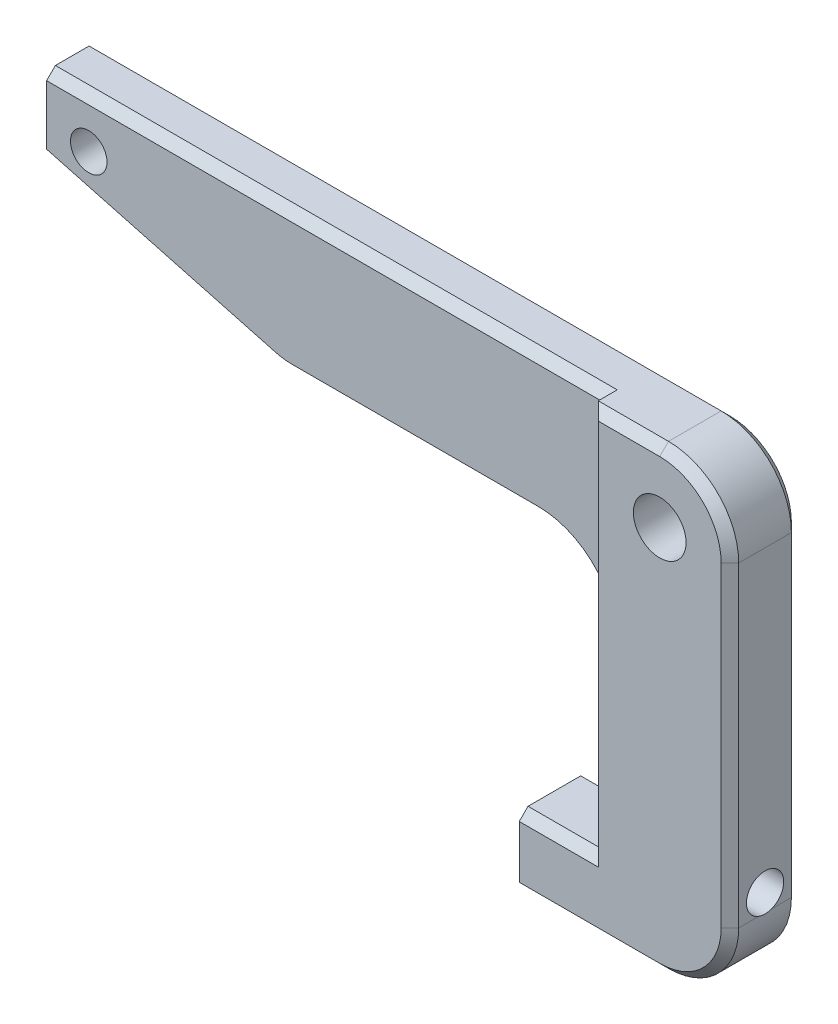
SolidWorks part; units mm, degrees
ref_plane "Plane1" through (0, 0, 0) normal (0, 0, 1) x (1, 0, 0)
ref_plane "Plane2" through (0, 0, 0) normal (0, 1, 0) x (1, 0, 0)
ref_plane "Plane3" through (0, 0, 0) normal (1, 0, 0) x (0, 0, -1)
other "Configuration Table"
sketch "Sketch1" plane through (0, 0, 0) normal (0, 0, 1) x (1, 0, 0)
  line L0 (-114.3, 12.7) -> (-114.3, -12.7)
  line L1 (-114.3, -12.7) -> (-12.7, -12.7)
  line L2 (12.7, 12.7) -> (-114.3, 12.7)
  line L3 (12.7, 12.7) -> (12.7, -69.85)
  line L4 (-12.7, -12.7) -> (-12.7, -57.15)
  line L5 (12.7, -69.85) -> (-25.4, -69.85)
  line L6 (-25.4, -69.85) -> (-25.4, -57.15)
  line L7 (-25.4, -57.15) -> (-12.7, -57.15)
  dimension "D1" = 82.55
  dimension "D2" = 127
  dimension "D3" = 44.45
  dimension "D4" = 25.4
  dimension "D5" = 12.7
  dimension "D6" = 12.7
  dimension "D7" = 25.4
  dimension "D8" = 38.1
extrude "Base-Extrude" add sketch "Sketch1" along normal blind 12.7
sketch "Sketch2" plane through (0, 0, 12.7) normal (0, 0, 1) x (1, 0, 0)
  circle A0 centre (0, 0) radius 4.7625
  dimension "D1" = 9.525
extrude "Cut-Extrude1" cut sketch "Sketch2" against normal through all
sketch "Sketch3" plane through (-40.8261, 4.3037, 12.7) normal (0, 0, 1) x (1, 0, 0)
  line L0 (-73.4739, 8.3963) -> (-73.4739, -17.0037) construction
  line L1 (53.5261, 8.3963) -> (-73.4739, 8.3963) construction
  circle A0 centre (-65.8539, -0.4937) radius 3.302
  dimension "D1" = 6.604
  dimension "D2" = 7.62
  dimension "D3" = 8.89
extrude "Cut-Extrude2" cut sketch "Sketch3" against normal through all
chamfer "Chamfer1" distance 11.43 angle 75 1 edges at (-114.3, -12.7, 6.35)
sketch "Sketch5" plane through (-65.558, -0.2007, 12.7) normal (0, 0, 1) x (1, 0, 0)
  line L0 (52.858, 12.9007) -> (-48.742, 12.9007)
  line L1 (52.858, 12.9007) -> (52.858, -12.4993)
  line L2 (-48.742, -12.4993) -> (52.858, -12.4993)
  line L3 (-48.742, -12.4993) -> (-48.742, 12.9007)
  line L4 (-48.742, 12.9007) -> (-48.742, -1.0693) construction
  line L5 (78.258, 12.9007) -> (-48.742, 12.9007) construction
  line L6 (52.858, -12.4993) -> (52.858, -56.9493) construction
  line L7 (-6.0847, -12.4993) -> (52.858, -12.4993) construction
extrude "Cut-Extrude4" cut sketch "Sketch5" against normal blind 3.429
hole_wizard "Hole1" positions "Sketch6" profile "Sketch7" legacy end condition through all
sketch "Sketch6" plane through (12.7, 0, 0) normal (1, 0, 0) x (0, 0, -1)
  line L0 (-6.35, -53.975) -> (-6.35, 12.7) construction
  line L1 (-12.7, 12.7) -> (0, 12.7) construction
  line L2 (0, 0) -> (-12.7, 0) construction
  point P0 (-6.35, -53.975)
  dimension "D1" = 53.975
sketch "Sketch7" plane through (12.7, -53.975, 6.35) normal (0, 1, 0) x (0, 0, -1)
  line L0 (0, 0) -> (0, 127)
  line L1 (0, 127) -> (2.1082, 127)
  line L2 (2.1082, 127) -> (2.1082, 126.9975)
  line L3 (2.1082, 126.9975) -> (2.1082, 12.7)
  line L4 (2.1082, 12.7) -> (2.7407, 12.7)
  line L5 (2.7407, 12.7) -> (3.3731, 12.7)
  line L6 (3.3731, 12.7) -> (3.3731, 6.35)
  line L7 (3.3731, 6.35) -> (3.3731, 0)
  line L8 (3.3731, 0) -> (0, 0)
fillet "Fillet2" radius 12.7 4 edges at (12.7, 12.7, 6.35) (12.7, -69.85, 6.35) (-71.6427, -12.7, 4.6355) (-12.7, -12.7, 4.6355)
chamfer "Chamfer2" distance 1.5875 angle 45 5 edges at (-57.15, 12.7, 0) (12.7, -28.575, 0) (-12.7, -69.85, 0) (8.9803, -66.1303, 0) (8.9803, 8.9803, 0)
chamfer "Chamfer3" distance 1.5875 angle 45 18 edges at (-93.7788, -6.7686, 0) (-71.6284, -12.5913, 0) (-47.6853, -12.7, 0) (-16.4197, -16.4197, 0) (-19.05, -57.15, 0) (-12.7, -41.275, 0) (-6.35, 12.7, 12.7) (-16.4197, -16.4197, 9.271) (8.9803, 8.9803, 12.7) (-47.6853, -12.7, 9.271) (-12.7, -69.85, 12.7) (12.7, -28.575, 12.7) (-71.6284, -12.5913, 9.271) (8.9803, -66.1303, 12.7) (-63.5, 12.7, 9.271) (-93.7788, -6.7686, 9.271) (-19.05, -57.15, 12.7) (-12.7, -22.225, 12.7)
sketch "Sketch8" plane through (0, 0, 0) normal (0, 0, -1) x (-1, 0, 0)
  circle A0 centre (0, 0) radius 9.525
  dimension "D1" = 19.05
extrude "Cut-Extrude5" cut sketch "Sketch8" against normal blind 4.7752
